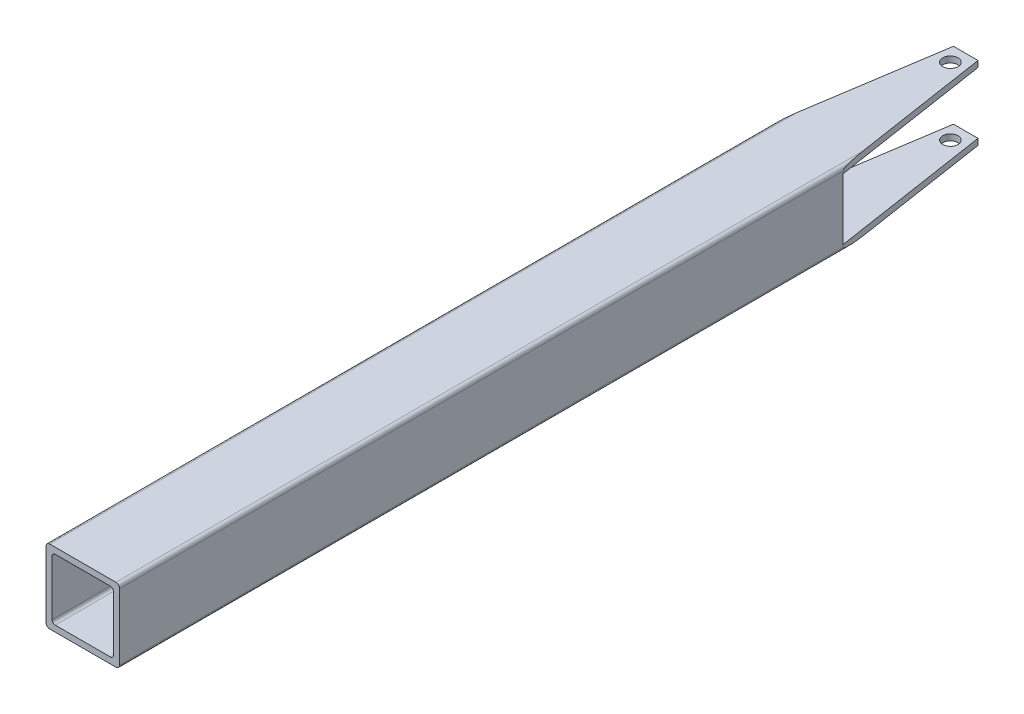
SolidWorks part; units mm, degrees
ref_plane "Front" through (0, 0, 0) normal (0, 0, 1) x (1, 0, 0)
ref_plane "Top" through (0, 0, 0) normal (0, 1, 0) x (1, 0, 0)
ref_plane "Right" through (0, 0, 0) normal (1, 0, 0) x (0, 0, -1)
sketch "Sketch1" plane through (0, 0, 0) normal (0, 0, 1) x (1, 0, 0)
  line L0 (-31.75, 0) -> (-38.1, 0) construction
  line L1 (34.29, -38.1) -> (-34.29, -38.1)
  line L2 (38.1, -34.29) -> (38.1, 34.29)
  line L3 (34.29, 38.1) -> (-34.29, 38.1)
  line L4 (-38.1, -34.29) -> (-38.1, 34.29)
  line L5 (38.1, -38.1) -> (-38.1, 38.1) construction
  line L6 (38.1, 38.1) -> (-38.1, -38.1) construction
  line L7 (28.575, 31.75) -> (-28.575, 31.75)
  line L8 (31.75, 28.575) -> (31.75, -28.575)
  line L9 (28.575, -31.75) -> (-28.575, -31.75)
  line L10 (-31.75, 28.575) -> (-31.75, -28.575)
  line L11 (31.75, 31.75) -> (-31.75, -31.75) construction
  line L12 (31.75, -31.75) -> (-31.75, 31.75) construction
  line L13 (0, -31.75) -> (0, -38.1) construction
  line L14 (31.75, -28.575) -> (31.75, -38.1) construction
  line L16 (31.75, -38.1) -> (38.1, -38.1) construction
  arc A0 (-28.575, -31.75) -> (-31.75, -28.575) centre (-28.575, -28.575) cw
  arc A1 (31.75, -28.575) -> (28.575, -31.75) centre (28.575, -28.575) cw
  arc A2 (28.575, 31.75) -> (31.75, 28.575) centre (28.575, 28.575) cw
  arc A3 (-28.575, 31.75) -> (-31.75, 28.575) centre (-28.575, 28.575) ccw
  arc A4 (34.29, -38.1) -> (38.1, -34.29) centre (34.29, -34.29) ccw
  arc A5 (38.1, 34.29) -> (34.29, 38.1) centre (34.29, 34.29) ccw
  arc A6 (-34.29, 38.1) -> (-38.1, 34.29) centre (-34.29, 34.29) ccw
  arc A7 (-34.29, -38.1) -> (-38.1, -34.29) centre (-34.29, -34.29) cw
  point P0 (0, 0)
  point P6 (0, 0)
  dimension "D2" = 3.175
  dimension "D3" = 3.81
sketch "Sketch2" plane through (0, 0, 0) normal (1, 0, 0) x (0, 0, -1)
  line L0 (-457.2, 0) -> (457.2, 0) construction
  dimension "Length" = 914.4
ref_plane "Plane1" through (38.1, 0, 0) normal (1, 0, 0) x (0, 0, -1)
sketch "Sketch5" plane through (38.1, 0, 0) normal (1, 0, 0) x (0, 0, -1)
  line L0 (-457.2, 38.1) -> (-457.2, -38.1) construction
  line L1 (457.2, 38.1) -> (457.2, -38.1) construction
sketch "Sketch4" plane through (0, 0, 0) normal (0, 0, 1) x (1, 0, 0)
  line L0 (38.1, -34.29) -> (38.1, 34.29) construction
  line L1 (34.29, 38.1) -> (-34.29, 38.1) construction
  line L2 (-38.1, -34.29) -> (-38.1, 34.29) construction
  line L3 (34.29, -38.1) -> (-34.29, -38.1) construction
  line L4 (31.75, 28.575) -> (31.75, -28.575) construction
  line L5 (28.575, -31.75) -> (-28.575, -31.75) construction
  line L6 (-31.75, 28.575) -> (-31.75, -28.575) construction
  line L7 (28.575, 31.75) -> (-28.575, 31.75) construction
  line L8 (38.1, -34.29) -> (38.1, 34.29)
  line L9 (34.29, 38.1) -> (-34.29, 38.1)
  line L10 (-38.1, -34.29) -> (-38.1, 34.29)
  line L11 (34.29, -38.1) -> (-34.29, -38.1)
  line L12 (31.75, 28.575) -> (31.75, -28.575)
  line L13 (28.575, -31.75) -> (-28.575, -31.75)
  line L14 (-31.75, 28.575) -> (-31.75, -28.575)
  line L15 (28.575, 31.75) -> (-28.575, 31.75)
  arc A0 (38.1, 34.29) -> (34.29, 38.1) centre (34.29, 34.29) ccw construction
  arc A1 (-34.29, 38.1) -> (-38.1, 34.29) centre (-34.29, 34.29) ccw construction
  arc A2 (-38.1, -34.29) -> (-34.29, -38.1) centre (-34.29, -34.29) ccw construction
  arc A3 (34.29, -38.1) -> (38.1, -34.29) centre (34.29, -34.29) ccw construction
  arc A4 (28.575, -31.75) -> (31.75, -28.575) centre (28.575, -28.575) ccw construction
  arc A5 (-31.75, -28.575) -> (-28.575, -31.75) centre (-28.575, -28.575) ccw construction
  arc A6 (-28.575, 31.75) -> (-31.75, 28.575) centre (-28.575, 28.575) ccw construction
  arc A7 (31.75, 28.575) -> (28.575, 31.75) centre (28.575, 28.575) ccw construction
  arc A8 (38.1, 34.29) -> (34.29, 38.1) centre (34.29, 34.29) ccw
  arc A9 (-34.29, 38.1) -> (-38.1, 34.29) centre (-34.29, 34.29) ccw
  arc A10 (-38.1, -34.29) -> (-34.29, -38.1) centre (-34.29, -34.29) ccw
  arc A11 (34.29, -38.1) -> (38.1, -34.29) centre (34.29, -34.29) ccw
  arc A12 (28.575, -31.75) -> (31.75, -28.575) centre (28.575, -28.575) ccw
  arc A13 (-31.75, -28.575) -> (-28.575, -31.75) centre (-28.575, -28.575) ccw
  arc A14 (-28.575, 31.75) -> (-31.75, 28.575) centre (-28.575, 28.575) ccw
  arc A15 (31.75, 28.575) -> (28.575, 31.75) centre (28.575, 28.575) ccw
extrude "Boss-Extrude1" add sketch "Sketch4" along normal up to vertex (457.2 mm away) and the other way up to vertex (457.2 mm away) up to point (0, 0, 457.2) other way up to point (0, 0, -457.2)
sketch "Sketch6" plane through (-38.1, 0, 0) normal (-1, 0, 0) x (0, 0, 1)
  line L0 (-457.2, -31.75) -> (-371.4675, -31.75) construction
  line L1 (-457.2, 31.75) -> (-292.1, 31.75)
  line L2 (-457.2, 31.75) -> (-457.2, -31.75)
  line L3 (-457.2, -31.75) -> (-292.1, -31.75)
  line L4 (-292.1, 31.75) -> (-292.1, -31.75)
  point P5 (-457.2, -31.75)
  dimension "D1" = 165.1
extrude "side cut" cut sketch "Sketch6" against normal through all
sketch "Sketch7" plane through (0, -38.1, 0) normal (0, -1, 0) x (1, 0, 0)
  line L0 (0, -457.2) -> (0, -341.7828) construction
  line L1 (-34.29, -457.2) -> (34.29, -457.2) construction
  line L2 (-38.1, -292.1) -> (-38.1, -457.2)
  line L3 (-38.1, -457.2) -> (-12.7, -457.2)
  line L4 (-12.7, -457.2) -> (-38.1, -292.1)
  line L5 (12.7, -457.2) -> (38.1, -292.1)
  line L6 (38.1, -457.2) -> (12.7, -457.2)
  line L7 (38.1, -292.1) -> (38.1, -457.2)
  dimension "D1" = 25.4
extrude "triangle cut" cut sketch "Sketch7" against normal through all
sketch "Sketch8" plane through (0, 38.1, 0) normal (0, 1, 0) x (1, 0, 0)
  line L0 (0, 457.2) -> (0, 353.4841) construction
  line L1 (12.7, 457.2) -> (-12.7, 457.2) construction
  circle A0 centre (0, 441.325) radius 7.9375
  dimension "D1" = 15.875
  dimension "D2" = 15.875
extrude "Cut-Extrude4" cut sketch "Sketch8" against normal through all
sketch "Sketch9" plane through (38.1, 0, 0) normal (1, 0, 0) x (0, 0, -1)
  line L0 (433.3875, 34.925) -> (449.2625, 34.925) construction
  line L1 (433.3875, 38.1) -> (433.3875, 31.75) construction
  line L2 (449.2625, 31.75) -> (449.2625, 38.1) construction
  line L3 (433.3875, -34.925) -> (449.2625, -34.925) construction
  line L4 (433.3875, -31.75) -> (433.3875, -38.1) construction
  line L5 (449.2625, -38.1) -> (449.2625, -31.75) construction
  line L6 (441.325, -34.925) -> (441.325, 34.925) construction
  line L7 (441.325, 0) -> (-193.675, 0)
  point P18 (-193.675, 0)
  dimension "D1" = 635
equation "\"D3@Sketch1\"=\"Outside Width@Sketch1\"*.05"
equation "\"D2@Sketch1\"=\"D1@Sketch1\"*.05"
equation "\"mountingPointDistance\"=25"
equation "\"D1@Sketch9\"=\"mountingPointDistance\""
